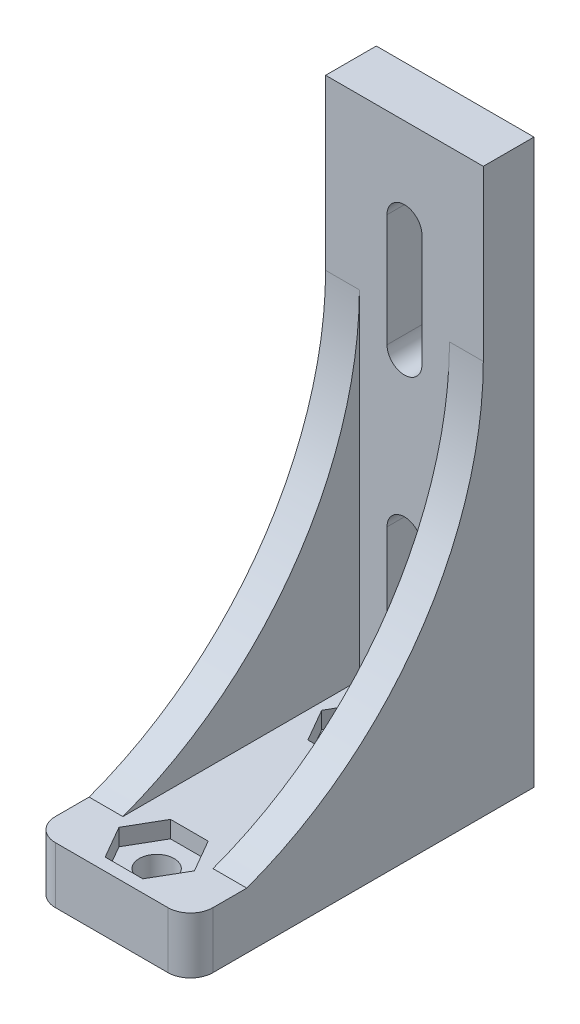
SolidWorks part; units mm, degrees
ref_plane "Alzado" through (0, 0, 0) normal (0, 0, 1) x (1, 0, 0)
ref_plane "Planta" through (0, 0, 0) normal (0, 1, 0) x (1, 0, 0)
ref_plane "Vista lateral" through (0, 0, 0) normal (1, 0, 0) x (0, 0, -1)
sketch "Croquis2" plane through (0, 0, 0) normal (0, 1, 0) x (1, 0, 0)
  line L0 (7, 31) -> (7, 0) construction
  line L1 (0, 0) -> (14, 0)
  line L2 (0, 0) -> (0, 31)
  line L3 (0, 31) -> (14, 31)
  line L4 (14, 0) -> (14, 31)
  circle A0 centre (7, 22) radius 1.55
  circle A1 centre (7, 4) radius 1.55
  dimension "D3" = 3.1
  dimension "D4" = 18
  dimension "D5" = 4
  dimension "D1" = 14
  dimension "D2" = 31
extrude "Saliente-Extruir1" add sketch "Croquis2" along normal blind 50
sketch "Croquis3" plane through (0, 0, 0) normal (-1, 0, 0) x (0, 0, 1)
  line L0 (-31, 50) -> (-31, 0) construction
  line L1 (0, 50) -> (-26, 50)
  line L2 (0, 50) -> (0, 5)
  line L3 (0, 5) -> (-26, 5)
  line L4 (-26, 50) -> (-26, 5)
  line L5 (-31, 0) -> (0, 0) construction
  dimension "D1" = 5
  dimension "D2" = 5
extrude "Cortar-Extruir1" cut sketch "Croquis3" against normal up to surface (14 mm away) up to face at (14, 25, -15.5)
sketch "Croquis4" plane through (0, 0, -31) normal (0, 0, -1) x (-1, 0, 0)
  line L0 (-7, 0) -> (-7, 50) construction
  line L1 (-14, 0) -> (0, 0) construction
  line L2 (-14, 50) -> (0, 50) construction
  line L3 (-14, 50) -> (-14, 0) construction
  line L5 (-7, 8) -> (-7, 18) construction
  line L6 (-8.55, 8) -> (-8.55, 18)
  line L7 (-5.45, 8) -> (-5.45, 18)
  line L8 (-7, 32) -> (-7, 42) construction
  line L9 (-8.55, 32) -> (-8.55, 42)
  line L10 (-5.45, 32) -> (-5.45, 42)
  arc A0 (-8.55, 8) -> (-5.45, 8) centre (-7, 8) ccw
  arc A1 (-5.45, 18) -> (-8.55, 18) centre (-7, 18) ccw
  arc A2 (-8.55, 32) -> (-5.45, 32) centre (-7, 32) ccw
  arc A3 (-5.45, 42) -> (-8.55, 42) centre (-7, 42) ccw
  point P8 (-7, 13)
  point P17 (-7, 37)
  dimension "D1" = 7
  dimension "D2" = 3.1
  dimension "D3" = 10
  dimension "D4" = 3.1
  dimension "D5" = 10
  dimension "D6" = 8
  dimension "D7" = 14
extrude "Cortar-Extruir2" cut sketch "Croquis4" against normal up to surface (5 mm away) up to face at (7, 27.5, -26)
sketch "Croquis5" plane through (0, 5, 0) normal (0, 1, 0) x (1, 0, 0)
  line L1 (10.3486, 4) -> (8.6743, 6.9)
  line L2 (8.6743, 6.9) -> (5.3257, 6.9)
  line L3 (5.3257, 6.9) -> (3.6514, 4)
  line L4 (3.6514, 4) -> (5.3257, 1.1)
  line L5 (5.3257, 1.1) -> (8.6743, 1.1)
  line L6 (8.6743, 1.1) -> (10.3486, 4)
  line L7 (8.6743, 19.1) -> (10.3486, 22)
  line L8 (10.3486, 22) -> (8.6743, 24.9)
  line L9 (8.6743, 24.9) -> (5.3257, 24.9)
  line L10 (5.3257, 24.9) -> (3.6514, 22)
  line L11 (3.6514, 22) -> (5.3257, 19.1)
  line L12 (5.3257, 19.1) -> (8.6743, 19.1)
  circle A0 centre (7, 4) radius 2.9 construction
  circle A1 centre (7, 22) radius 2.9 construction
  dimension "D1" = 5.8
  dimension "D2" = 5.8
extrude "Cortar-Extruir3" cut sketch "Croquis5" against normal blind 1.5
sketch "Croquis6" plane through (0, 0, 0) normal (-1, 0, 0) x (0, 0, 1)
  line L3 (-26, 50) -> (-26, 5) construction
  line L9 (-26, 5) -> (0, 5) construction
  line L10 (-31, 50) -> (-26, 50) construction
  line L11 (0, 5) -> (0, 0) construction
  line L12 (-26, 5) -> (-26, 35)
  line L13 (-26, 5) -> (-5, 5)
  arc A1 (-26, 35) -> (-5, 5) centre (5.9975, 35.0482) ccw
  dimension "D1" = 15
  dimension "D2" = 5
extrude "Saliente-Extruir3" add sketch "Croquis6" against normal up to surface (14 mm away) up to face at (14, 18.3333, -19)
sketch "Croquis7" plane through (0, 50, 0) normal (0, 1, 0) x (1, 0, 0)
  line L0 (14, 0) -> (0, 0) construction
  line L2 (0, 26) -> (0, 0)
  line L3 (0, 0) -> (3, 0)
  line L4 (3, 26) -> (3, 0)
  line L7 (14, 26) -> (14, 0)
  line L8 (14, 0) -> (11, 0)
  line L9 (11, 26) -> (11, 0)
  line L10 (3, 26) -> (11, 26)
  line L11 (0, 26) -> (0, 31)
  line L12 (0, 31) -> (14, 31)
  line L13 (14, 26) -> (14, 31)
  dimension "D1" = 3
  dimension "D2" = 3
  dimension "D3" = 5
extrude "Cortar-Extruir5" cut sketch "Croquis7" against normal up to surface (45 mm away) flip side to cut up to face at (7, 5, -3.02)
fillet "Redondeo1" radius 2 2 edges at (14, 2.5, 0) (0, 2.5, 0)
sketch "Croquis8" plane through (0, 50, 0) normal (0, 1, 0) x (1, 0, 0)
  line L11 (14, 26) -> (14, 31) construction
  line L12 (0, 31) -> (14, 31)
  line L13 (0, 31) -> (0, 30.5)
  line L14 (0, 30.5) -> (14, 30.5)
  line L15 (14, 31) -> (14, 30.5)
  dimension "D1" = 0.5
extrude "Cortar-Extruir6" cut sketch "Croquis8" against normal up to surface (50 mm away) up to face at (7, 0, -20.45)
